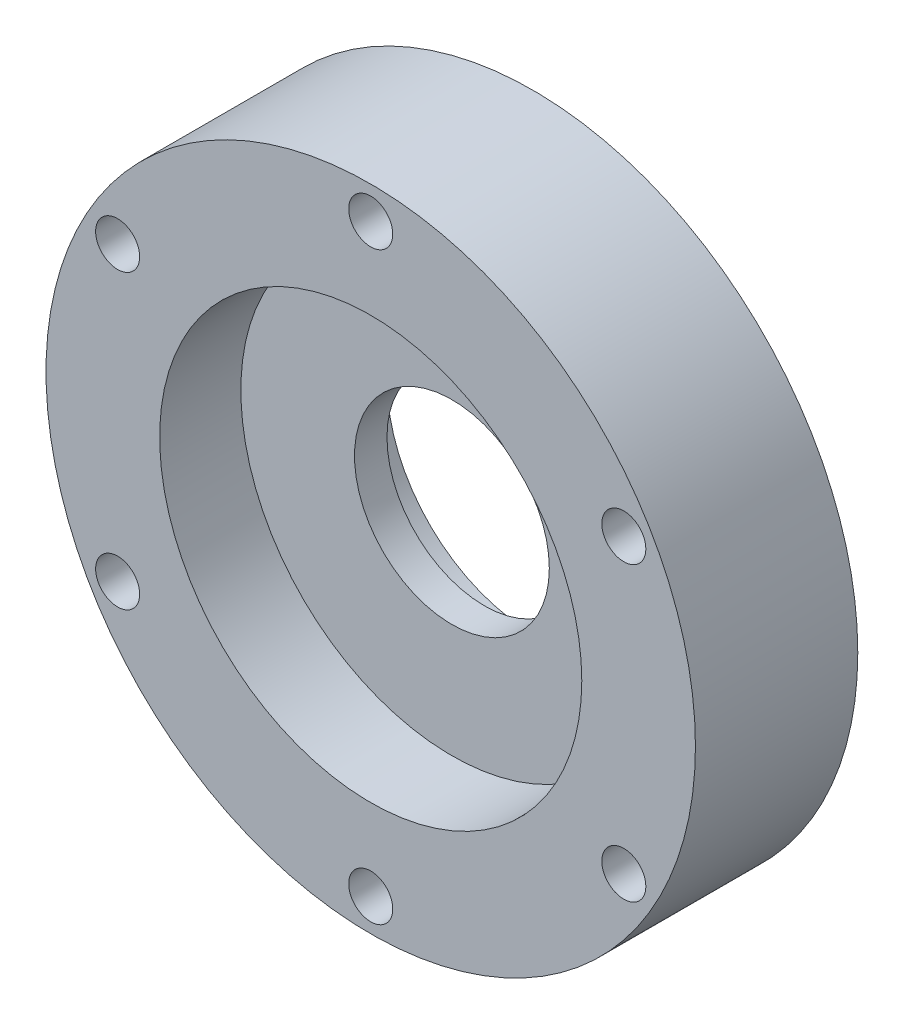
SolidWorks part; units mm, degrees
material "6061-T6 (SS)"
ref_plane "Front Plane" through (0, 0, 0) normal (0, 0, 1) x (1, 0, 0)
ref_plane "Top Plane" through (0, 0, 0) normal (0, 1, 0) x (1, 0, 0)
ref_plane "Right Plane" through (0, 0, 0) normal (1, 0, 0) x (0, 0, -1)
sketch "Sketch1" plane through (0, 0, 0) normal (0, 0, 1) x (1, 0, 0)
  circle A0 centre (0, 0) radius 31.75
  dimension "D1" = 63.5
extrude "Boss-Extrude1" add sketch "Sketch1" along normal blind 15.875
sketch "Sketch2" plane through (0, 0, 15.875) normal (0, 0, 1) x (1, 0, 0)
  circle A0 centre (0, 0) radius 20.6375
  dimension "D1" = 41.275
extrude "Cut-Extrude1" cut sketch "Sketch2" against normal blind 7.9375
sketch "Sketch3" plane through (0, 0, 0) normal (0, 0, -1) x (-1, 0, 0)
  circle A0 centre (0, 0) radius 14.2875
  dimension "D1" = 28.575
extrude "Cut-Extrude2" cut sketch "Sketch3" against normal blind 4.7625
sketch "Sketch4" plane through (0, 0, 7.9375) normal (0, 0, 1) x (1, 0, 0)
  circle A0 centre (0, 0) radius 9.525
  dimension "D1" = 19.05
extrude "Cut-Extrude3" cut sketch "Sketch4" against normal through all
hole_wizard "#8 Clearance Hole1" positions "Sketch6" profile "Sketch7" hole size "#8" standard "Ansi Inch" end condition through all
sketch "Sketch6" plane through (0, 0, 15.875) normal (0, 0, 1) x (1, 0, 0)
  point P0 (0, 28.575)
  point P9 (24.7467, 14.2875)
  point P10 (24.7467, -14.2875)
  point P11 (0, -28.575)
  point P12 (-24.7467, -14.2875)
  point P13 (-24.7467, 14.2875)
  dimension "D1" = 28.575
sketch "Sketch7" plane through (0, 28.575, 15.875) normal (1, 0, 0) x (0, -1, 0)
  line L0 (0, 0) -> (0, 15.875)
  line L1 (0, 15.875) -> (2.1526, 15.875)
  line L2 (2.1526, 15.875) -> (2.1526, 0)
  line L5 (2.1526, 0) -> (0, 0)
  line L11 (0, -6.35) -> (0, 107.95) construction
  dimension "Thru Hole Dia." = 4.3053
  dimension "Thru Hole Depth" = 15.875
sketch "Sketch8" plane through (0, 0, 0) normal (0, 0, -1) x (-1, 0, 0)
  line L0 (0, 26.4224) -> (0, 22.225)
  line L1 (24.7467, 14.2875) -> (18.8416, 10.8782)
  line L2 (0.7874, 24.4469) -> (0.7874, 23.6938)
  line L3 (20.7779, 12.9054) -> (20.1257, 12.5288)
  arc A0 (23.2539, 19.2102) -> (5.0096, 29.7436) centre (0, 0) ccw
  arc A1 (18.0432, 12.9767) -> (2.2166, 22.1142) centre (0, 0) ccw
  arc A2 (1.5833, 25.8229) -> (3.164, 28.3104) centre (0, 28.575) ccw
  arc A3 (22.9356, 16.8953) -> (21.5717, 14.2826) centre (24.7467, 14.2875) ccw
  circle A4 centre (0, 28.575) radius 2.1526 construction
  arc A5 (23.2539, 19.2102) -> (22.9356, 16.8953) centre (22.03, 18.1992) cw
  arc A6 (21.5717, 14.2826) -> (20.7779, 12.9054) centre (19.9842, 14.2802) cw
  arc A7 (20.1257, 12.5288) -> (18.0432, 12.9767) centre (19.332, 13.9036) cw
  arc A8 (2.2166, 22.1142) -> (0.7874, 23.6938) centre (2.3749, 23.6938) cw
  arc A9 (0.7874, 24.4469) -> (1.5833, 25.8229) centre (2.3749, 24.4469) cw
  arc A10 (3.164, 28.3104) -> (5.0096, 29.7436) centre (4.7459, 28.1781) cw
  point P24 (18.8416, 11.7874)
  dimension "D1" = 60.325
  dimension "D2" = 44.45
  dimension "D3" = 6.35
  dimension "D4" = 6.35
  dimension "D7" = 1.5875
  dimension "D5" = 0.7874
  dimension "D6" = 0.7874
extrude "Cut-Extrude4" cut sketch "Sketch8" against normal blind 12.7 contours A10 A2 A9 L2 A8 A1 A7 L3 A6 A3 A5 A0 region at (-12.6837, 21.9687, 0)
pattern_circular "CirPattern1" count 6 over 360 about axis through (0, 0, 0) along (0, 0, 1) of "Cut-Extrude4"
sketch "Sketch9" plane through (0, 0, 0) normal (0, 0, -1) x (-1, 0, 0)
  line L0 (0, 24.2331) -> (0, 15.875)
  line L1 (24.7467, 14.2875) -> (13.3375, 7.7004)
  line L2 (0.7874, 24.4469) -> (0.7874, 17.3003)
  line L3 (20.7779, 12.9054) -> (14.5888, 9.332)
  arc A0 (23.2539, 19.2102) -> (5.0096, 29.7436) centre (0, 0) ccw
  arc A1 (12.5409, 9.7335) -> (2.159, 15.7275) centre (0, 0) ccw
  arc A2 (1.5833, 25.8229) -> (3.164, 28.3104) centre (0, 28.575) ccw
  arc A3 (22.9356, 16.8953) -> (21.5717, 14.2826) centre (24.7467, 14.2875) ccw
  arc A5 (23.2539, 19.2102) -> (22.9356, 16.8953) centre (22.03, 18.1992) cw
  arc A6 (21.5717, 14.2826) -> (20.7779, 12.9054) centre (19.9842, 14.2802) cw
  arc A7 (14.5888, 9.332) -> (12.5409, 9.7335) centre (13.795, 10.7069) cw
  arc A8 (2.159, 15.7275) -> (0.7874, 17.3003) centre (2.3749, 17.3003) cw
  arc A9 (0.7874, 24.4469) -> (1.5833, 25.8229) centre (2.3749, 24.4469) cw
  arc A10 (3.164, 28.3104) -> (5.0096, 29.7436) centre (4.7459, 28.1781) cw
  circle A11 centre (0, 0) radius 31.75 construction
  circle A12 centre (24.7467, 14.2875) radius 2.1526 construction
  circle A13 centre (0, 28.575) radius 2.1526 construction
  point P24 (13.3375, 8.6096)
  dimension "D1" = 60.325
  dimension "D2" = 15.875
  dimension "D3" = 6.35
  dimension "D4" = 6.35
  dimension "D7" = 1.5875
  dimension "D5" = 0.7874
  dimension "D6" = 0.7874
extrude "Cut-Extrude5" cut sketch "Sketch9" against normal blind 4.7625 contours A10 A2 A9 L2 A8 A1 A7 L3 A6 A3 A5 A0 region at (-11.361, 19.6779, 0)
pattern_circular "CirPattern2" count 6 over 360 about axis through (0, 0, 0) along (0, 0, 1) of "Cut-Extrude5"
